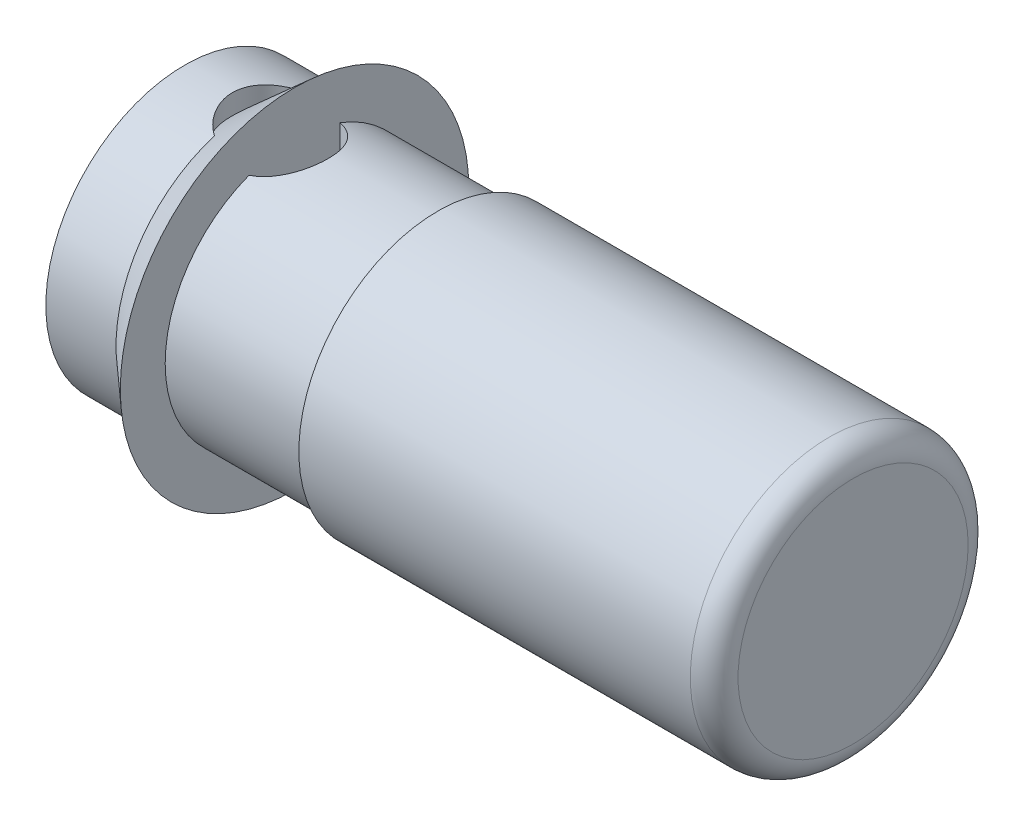
SolidWorks part; units mm, degrees
ref_plane "Front Plane" through (0, 0, 0) normal (0, 0, 1) x (1, 0, 0)
ref_plane "Top Plane" through (0, 0, 0) normal (0, 1, 0) x (1, 0, 0)
ref_plane "Right Plane" through (0, 0, 0) normal (1, 0, 0) x (0, 0, -1)
sketch "Sketch2" plane through (0, 0, 0) normal (1, 0, 0) x (0, 0, -1)
  circle A0 centre (0, 0) radius 1.455
  dimension "D1" = 2.91
extrude "Boss-Extrude3" add sketch "Sketch2" along normal blind 6 contours A0
sketch "Sketch3" plane through (6, 0, 0) normal (1, 0, 0) x (0, 0, -1)
  circle A0 centre (0, 0) radius 2.5
  dimension "D1" = 5
extrude "Boss-Extrude4" add sketch "Sketch3" along normal blind 2
sketch "Sketch4" plane through (0, 0, 0) normal (0, 1, 0) x (1, 0, 0)
  circle A0 centre (1, 0) radius 0.5
  dimension "D1" = 1
  dimension "D2" = 1
extrude "Cut-Extrude1" cut sketch "Sketch4" against normal through all both and the other way through all
ref_axis "Axis2" through (1, -1.455, 0) along (0, 1, 0)
ref_plane "Plane1" through (1, 0, 0) normal (1, 0, 0) x (0, 1, 0)
sketch "Sketch6" plane through (1, 0, 0) normal (1, 0, 0) x (0, 1, 0)
  circle A0 centre (0, 0) radius 1.575
  dimension "D1" = 3.15
extrude "Boss-Extrude5" add sketch "Sketch6" along normal blind 0.15
sketch "Sketch7" plane through (0, 0, 0) normal (0, 0, 1) x (1, 0, 0)
  line L0 (1.15, 1.825) -> (0, 0.8)
  line L1 (0, 0.8) -> (1.15, 0.8)
  line L2 (1.15, 0.8) -> (1.15, 1.825)
  dimension "D1" = 0
  dimension "D2" = 0
  dimension "D3" = 0.25
  dimension "D4" = 0.8
  dimension "D5" = 0
ref_axis "Axis1" through (9.45, 0, 0) along (-1, 0, 0)
revolve "Revolve1" add sketch "Sketch7" angle 360 about axis through (9.45, 0, 0) along (-1, 0, 0)
sketch "Sketch9" plane through (8, 0, 0) normal (1, 0, 0) x (0, 0, -1)
  circle A0 centre (0, 0) radius 2.5
  circle A1 centre (0, 0) radius 1.455
  circle A2 centre (0, 0) radius 1.455 construction
  dimension "D1" = 0
extrude "Cut-Extrude3" cut sketch "Sketch9" against normal up to next
sketch "Sketch10" plane through (8, 0, 0) normal (1, 0, 0) x (0, 0, -1)
  circle A0 centre (0, 0) radius 1.455
extrude "Cut-Extrude4" cut sketch "Sketch10" against normal blind 1
fillet "Fillet1" radius 0.25 1 edges at (7, 0, -1.455)
sketch "Sketch11" plane through (1.15, 0, 0) normal (1, 0, 0) x (0, 0, -1)
  circle A0 centre (0, 0) radius 1.355
  arc A1 (0.477, -1.3746) -> (0.477, 1.3746) centre (0, 0) ccw construction
  circle A2 centre (0, 0) radius 1.455
  dimension "D1" = 0.1
extrude "Cut-Extrude5" cut sketch "Sketch11" along normal blind 1.5
